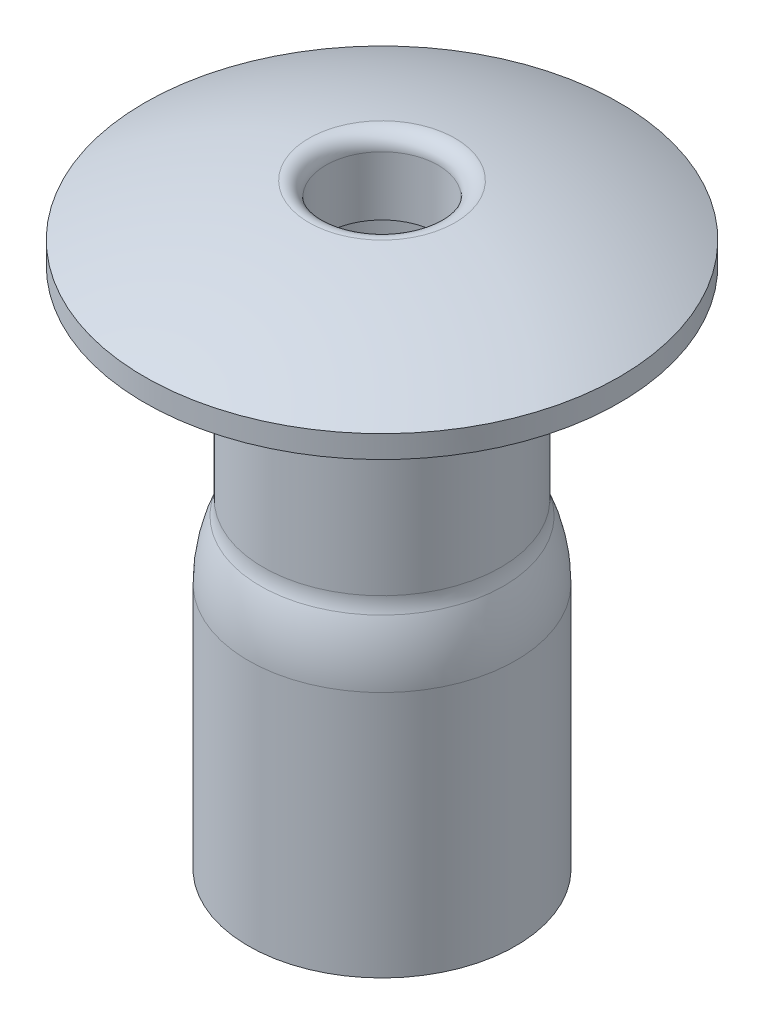
SolidWorks part; units mm, degrees
material "AISI 304"
ref_plane "Front Plane" through (0, 0, 0) normal (0, 0, 1) x (1, 0, 0)
ref_plane "Top Plane" through (0, 0, 0) normal (0, 1, 0) x (1, 0, 0)
ref_plane "Right Plane" through (0, 0, 0) normal (1, 0, 0) x (0, 0, -1)
ref_axis "Axis1" through (0, -13.2213, 0) along (0, 1, 0)
sketch "Sketch1" plane through (0, 0, 0) normal (0, 0, 1) x (1, 0, 0)
  line L0 (1.5875, -3.6798) -> (1.5875, -6.985)
  line L1 (0, 1.016) -> (0, -6.985) construction
  line L2 (3.175, 0.3) -> (3.175, 0)
  line L3 (3.175, 0) -> (1.5875, 0)
  line L4 (1.5875, 0) -> (1.5875, -2.7)
  line L5 (0, 0) -> (0, 1.016) construction
  line L6 (1.3875, -2.7) -> (1.3875, 0)
  line L7 (1.3875, 0) -> (0.75, 0)
  line L8 (1.7875, -3.6798) -> (1.7875, -6.985)
  line L9 (1.5875, -6.985) -> (1.7875, -6.985)
  line L10 (1.6637, -3) -> (10.1449, -3) construction
  line L11 (1.6637, -3) -> (1.6637, 0) construction
  line L12 (1.6637, 0) -> (9.9319, 0) construction
  line L13 (0.75, 0) -> (0.75, 1.016)
  line L14 (0, 1.016) -> (0.75, 1.016) construction
  arc A0 (1.5875, -2.7) -> (1.6275, -2.896) centre (2.0875, -2.7) ccw
  arc A1 (1.6275, -2.896) -> (1.7875, -3.6798) centre (-0.2125, -3.6798) cw
  arc A2 (1.5875, -3.6798) -> (1.4435, -2.9743) centre (-0.2125, -3.6798) ccw
  arc A3 (1.4435, -2.9743) -> (1.3875, -2.7) centre (2.0875, -2.7) cw
  arc A4 (0.75, 1.016) -> (3.175, 0.3) centre (0, -5.9887) cw
  point P20 (1.3875, -1.35)
  dimension "D6" = 0.5
  dimension "D8" = 2
  dimension "D1" = 6.35
  dimension "D2" = 1.016
  dimension "D3" = 0.3
  dimension "D4" = 3.175
  dimension "D5" = 0.2
  dimension "D7" = 6.985
  dimension "D9" = 1.5
  dimension "D10" = 3
  dimension "D11" = 3.3274
  dimension "D12" = 0.3
revolve "Revolve1" add sketch "Sketch1" angle 360 about L1
fillet "Fillet1" radius 0.2 1 edges at (-0.75, 1.016, 0)
